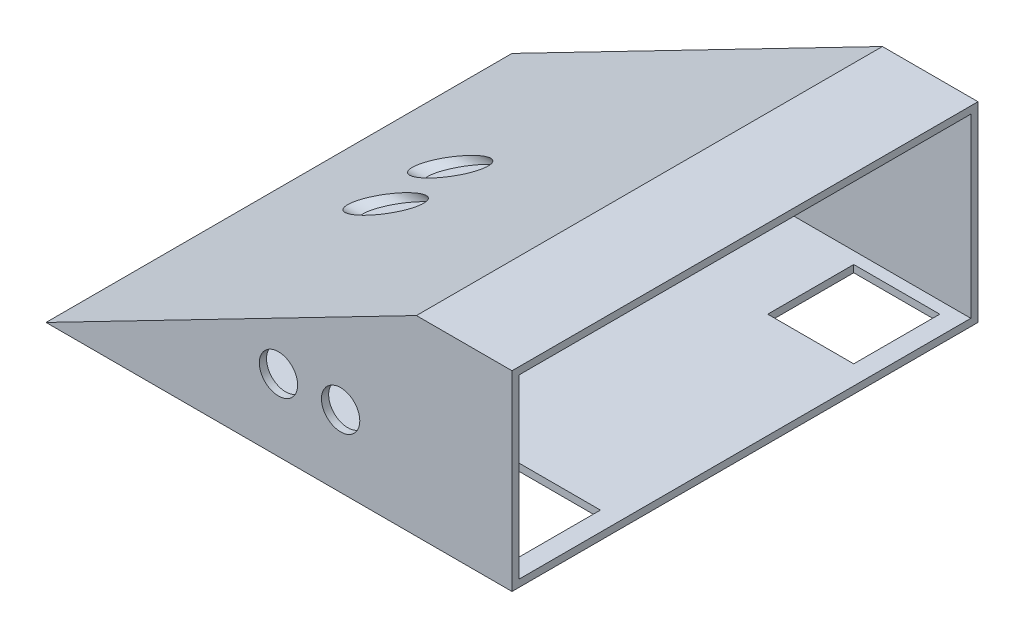
SolidWorks part; units mm, degrees
ref_plane "Front Plane" through (0, 0, 0) normal (0, 0, 1) x (1, 0, 0)
ref_plane "Top Plane" through (0, 0, 0) normal (0, 1, 0) x (1, 0, 0)
ref_plane "Right Plane" through (0, 0, 0) normal (1, 0, 0) x (0, 0, -1)
ref_plane "Plane1" through (0, 0, 0) normal (1, 0, 0) x (0, 0, -1)
ref_plane "Plane2" through (0, 0, 97.5) normal (0, 0, 1) x (1, 0, 0)
ref_plane "Plane3" through (75, 0, 0) normal (1, 0, 0) x (0, 0, -1)
sketch "Sketch2" plane through (0, 0, 0) normal (0, 0, 1) x (1, 0, 0)
  line L0 (0, 0) -> (195, 0)
  line L1 (195, 0) -> (195, 80)
  line L2 (195, 80) -> (155, 80)
  line L3 (155, 80) -> (0, 0)
  dimension "D1" = 195
  dimension "D2" = 40
  dimension "80" = 80
extrude "Robot" add sketch "Sketch2" along normal blind 195
sketch "Sketch3" plane through (0, 0, 195) normal (0, 0, 1) x (1, 0, 0)
  line L0 (0, 0) -> (195, 0) construction
  circle A0 centre (97.2899, 30) radius 8.02
  circle A1 centre (123.2899, 30) radius 8.02
  dimension "D1" = 30
  dimension "D2" = 16.04
  dimension "D4" = 16.04
  dimension "D3" = 26
  dimension "D5" = 30
sketch "Arriba" plane through (0, 80, 0) normal (0, 1, 0) x (1, 0, 0)
  line L0 (195, 0) -> (195, -195) construction
  line L1 (0, 0) -> (0, -195) construction
  line L2 (0, -97.5) -> (195, -97.5) construction
  line L3 (0, 0) -> (195, 0) construction
  line L4 (0, -195) -> (195, -195) construction
  line L5 (97.5, 0) -> (97.5, -195) construction
sketch "Adelante" plane through (0, 0, 0) normal (1, 0, 0) x (0, 0, -1)
  line L0 (0, 80) -> (0, 0) construction
  line L1 (-97.5, 80) -> (-97.5, 0) construction
  line L2 (0, 80) -> (-195, 80) construction
  line L3 (-195, 0) -> (0, 0) construction
  line L4 (-195, 80) -> (-195, 0) construction
  line L5 (0, 0) -> (-195, 0) construction
sketch "Sketch9" plane through (0, 0, 0) normal (0, 0, -1) x (-1, 0, 0)
  line L1 (0, 0) -> (-195, 0) construction
  circle A0 centre (-97.284, 30) radius 8.2
  circle A1 centre (-123.284, 30) radius 8.2
  dimension "D2" = 16.4
  dimension "D4" = 30
  dimension "D6" = 16.4
  dimension "D3" = 30
  dimension "D5" = 26
sketch "Sketch10" plane through (0, 0, 0) normal (0, -1, 0) x (-1, 0, 0)
  line L0 (0, -195) -> (-195, -195) construction
  line L1 (-187, -187) -> (-150, -187)
  line L2 (-187, -187) -> (-187, -150)
  line L3 (-187, -150) -> (-150, -150)
  line L4 (-150, -187) -> (-150, -150)
  line L5 (-195, 0) -> (-195, -195) construction
  dimension "D1" = 8
  dimension "D2" = 8
  dimension "D3" = 37
  dimension "D4" = 37
sketch "Sketch12" plane through (0, 0, 0) normal (0, -1, 0) x (-1, 0, 0)
  line L0 (-195, 0) -> (-195, -195) construction
  line L1 (-187, -44) -> (-151, -44)
  line L2 (-187, -44) -> (-187, -8)
  line L3 (-187, -8) -> (-151, -8)
  line L4 (-151, -44) -> (-151, -8)
  line L5 (0, 0) -> (-195, 0) construction
  dimension "D1" = 8
  dimension "D2" = 8
  dimension "D3" = 36
  dimension "D4" = 36
sketch "Sketch13" plane through (0, 0, 0) normal (0, -1, 0) x (1, 0, 0)
  line L0 (0, 0) -> (195, 0) construction
  line L1 (15, 8) -> (22.1, 8)
  line L2 (15, 8) -> (15, 15.1)
  line L3 (15, 15.1) -> (22.1, 15.1)
  line L4 (22.1, 8) -> (22.1, 15.1)
  line L5 (0, 0) -> (0, 195) construction
  dimension "D1" = 8
  dimension "D2" = 15
  dimension "D3" = 7.1
  dimension "D4" = 7.1
sketch "Sketch14" plane through (0, 0, 0) normal (0, -1, 0) x (-1, 0, 0)
  line L0 (0, -195) -> (-195, -195) construction
  line L1 (-15, -179.9) -> (-22.1, -179.9)
  line L2 (-15, -179.9) -> (-15, -187)
  line L3 (-15, -187) -> (-22.1, -187)
  line L4 (-22.1, -179.9) -> (-22.1, -187)
  line L5 (0, 0) -> (0, -195) construction
  dimension "D1" = 8
  dimension "D2" = 15
  dimension "D3" = 7.1
  dimension "D4" = 7.1
sketch "Sketch15" plane through (0, 0, 0) normal (0, -1, 0) x (-1, 0, 0)
  line L0 (0, -97.5) -> (-195, -97.5) construction
  line L1 (-15, -93.95) -> (-22.1, -93.95)
  line L2 (-15, -93.95) -> (-15, -101.05)
  line L3 (-15, -101.05) -> (-22.1, -101.05)
  line L4 (-22.1, -93.95) -> (-22.1, -101.05)
  line L5 (0, 0) -> (0, -195) construction
  dimension "D1" = 3.55
  dimension "D2" = 3.55
  dimension "D3" = 7.1
  dimension "D4" = 15
shell "Vacio por dentro 3mm" thickness 3 removed face at (195, 40, 97.5)
extrude "Ultrasonico Derecha" cut sketch "Sketch3" against normal blind 3
sketch "Ultrasonico Centro " plane through (0, 0, 0) normal (1, 0, 0) x (0, 0, -1)
  line L0 (0, 0) -> (-195, 0) construction
  line L1 (-97.5, 80) -> (-97.5, 0) construction
  circle A0 centre (-84, 30) radius 8.2
  circle A1 centre (-111, 30) radius 8.2
  dimension "D2" = 16.4
  dimension "D4" = 16.4
  dimension "D1" = 30
  dimension "D3" = 13.5
  dimension "D5" = 13.5
  dimension "D6" = 30
extrude "Ultrasonico Izquierda" cut sketch "Sketch9" against normal blind 3
extrude "Rueda Derecha" cut sketch "Sketch10" against normal blind 3
extrude "Rueda Izquierda" cut sketch "Sketch12" against normal blind 3
extrude "Cyn70 Derecha" cut sketch "Sketch14" against normal blind 4
extrude "Cny70 Centro" cut sketch "Sketch15" against normal blind 4
extrude "Cny70 Izquierda" cut sketch "Sketch13" against normal blind 4
extrude "Cut-Extrude4" cut sketch "Ultrasonico Centro " along normal blind 75
